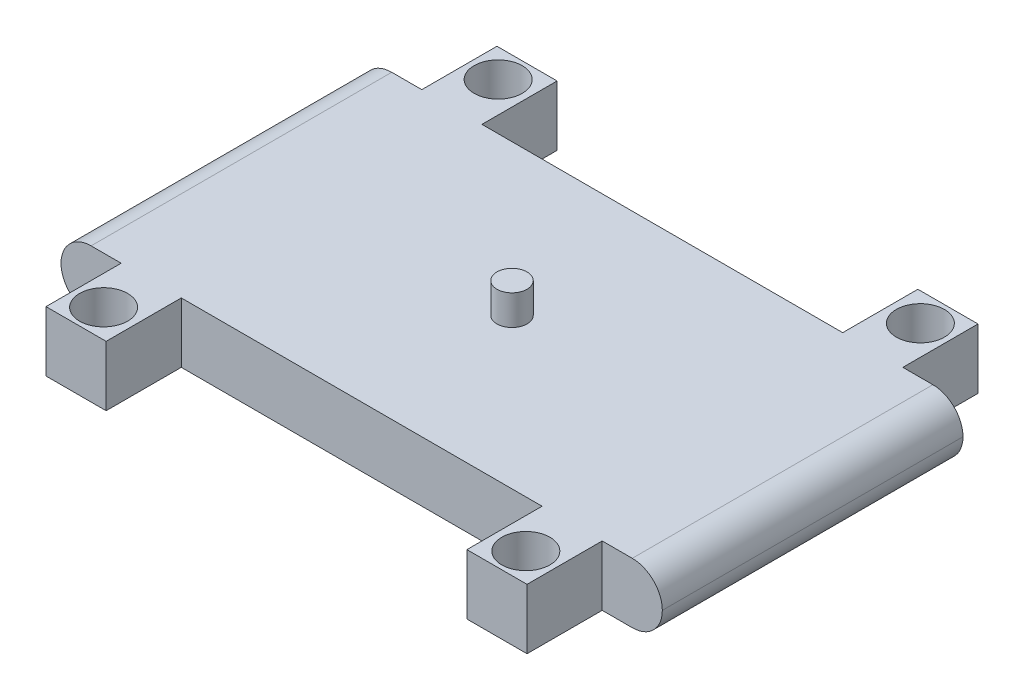
SolidWorks part; units mm, degrees
material "PE Low Density Film"
ref_plane "Front Plane" through (0, 0, 0) normal (0, 0, 1) x (1, 0, 0)
ref_plane "Top Plane" through (0, 0, 0) normal (0, 1, 0) x (1, 0, 0)
ref_plane "Right Plane" through (0, 0, 0) normal (1, 0, 0) x (0, 0, -1)
sketch "Sketch1" plane through (0, 0, 0) normal (0, 1, 0) x (1, 0, 0)
  line L1 (100, -50) -> (-100, -50)
  line L2 (100, -50) -> (100, 50)
  line L3 (100, 50) -> (-100, 50)
  line L4 (-100, -50) -> (-100, 50)
  line L5 (100, -50) -> (-100, 50) construction
  line L6 (100, 50) -> (-100, -50) construction
  point P0 (0, 0)
  dimension "D1" = 100
  dimension "D2" = 200
extrude "Boss-Extrude1" add sketch "Sketch1" along normal blind 20
sketch "Sketch2" plane through (0, 0, 0) normal (0, 0, 1) x (1, 0, 0)
  line L0 (-80, 20) -> (-80, 0)
  line L1 (-100, 20) -> (100, 20) construction
  line L2 (-100, 0) -> (100, 0) construction
  line L3 (-80, 0) -> (-60, 0)
  line L4 (-60, 0) -> (-60, 20)
  line L5 (-60, 20) -> (-80, 20)
  dimension "D1" = 20
  dimension "D2" = 20
  dimension "D3" = 20
extrude "Boss-Extrude2" add sketch "Sketch2" along normal mid plane 150
sketch "Sketch3" plane through (0, 0, 0) normal (0, 0, 1) x (1, 0, 0)
  line L0 (-60, 20) -> (100, 20) construction
  line L1 (80, 20) -> (60, 20)
  line L2 (80, 20) -> (80, 0)
  line L3 (80, 0) -> (60, 0)
  line L4 (60, 20) -> (60, 0)
  line L5 (-60, 0) -> (100, 0) construction
  dimension "D1" = 20
  dimension "D2" = 20
extrude "Boss-Extrude3" add sketch "Sketch3" along normal mid plane 150
sketch "Sketch4" plane through (0, 0, 0) normal (0, 1, 0) x (1, 0, 0)
  line L5 (70.2217, -65.6167) -> (-70.2217, 65.6167) construction
  line L6 (70.2217, 65.6167) -> (-70.2217, -65.6167) construction
  circle A0 centre (-70.2217, 65.6167) radius 8
  circle A1 centre (70.2217, 65.6167) radius 8
  circle A2 centre (-70.2217, -65.6167) radius 8
  circle A3 centre (70.2217, -65.6167) radius 8
  point P0 (0, 0)
extrude "Cut-Extrude1" cut sketch "Sketch4" along normal blind 150
sketch "Sketch5" plane through (0, 0, 0) normal (0, 1, 0) x (1, 0, 0)
  line L0 (70.2217, 65.6167) -> (-70.2217, -65.6167) construction
  circle A0 centre (0, 0) radius 5
extrude "Boss-Extrude4" add sketch "Sketch5" along normal blind 30
fillet "Fillet3" radius 10 2 edges at (100, 0, 0) (100, 20, 0)
fillet "Fillet4" radius 10 2 edges at (-100, 0, 0) (-100, 20, 0)
